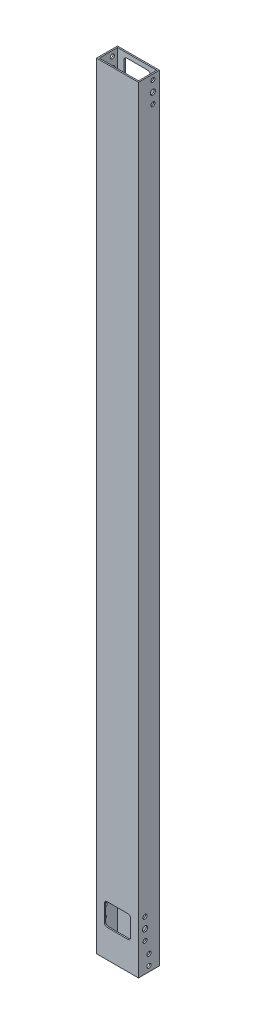
SolidWorks part; units mm, degrees
material "6061-T6 (SS)"
ref_plane "Front Plane" through (0, 0, 0) normal (0, 0, 1) x (1, 0, 0)
ref_plane "Top Plane" through (0, 0, 0) normal (0, 1, 0) x (1, 0, 0)
ref_plane "Right Plane" through (0, 0, 0) normal (1, 0, 0) x (0, 0, -1)
sketch "Sketch1" plane through (0, 0, 0) normal (0, 0, 1) x (1, 0, 0)
  line L1 (-25.4, -469.9) -> (25.4, -469.9)
  line L2 (-25.4, -469.9) -> (-25.4, 469.9)
  line L3 (-25.4, 469.9) -> (25.4, 469.9)
  line L4 (25.4, -469.9) -> (25.4, 469.9)
  line L5 (-25.4, -469.9) -> (25.4, 469.9) construction
  line L6 (-25.4, 469.9) -> (25.4, -469.9) construction
  point P0 (0, 0)
  dimension "D1" = 50.8
  dimension "D2" = 939.8
extrude "Boss-Extrude1" add sketch "Sketch1" along normal mid plane 25.4
shell "Shell1" thickness 1.5875 removed face at (0, -469.9, 0) removed face at (0, 469.9, 0)
sketch "Sketch3" plane through (0, 0, 0) normal (1, 0, 0) x (0, 0, -1)
  line L0 (-12.7, -469.9) -> (12.7, -469.9) construction
  circle A0 centre (0, -463.55) radius 2.4892
  circle A1 centre (0, -450.85) radius 2.4892
  point P6 (0, -469.9)
  dimension "D1" = 4.9784
  dimension "D2" = 6.35
  dimension "D3" = 12.7
extrude "Cut-Extrude1" cut sketch "Sketch3" against normal through all both and the other way through all
sketch "Sketch4" plane through (0, 0, 0) normal (1, 0, 0) x (0, 0, -1)
  line L4 (-12.7, -469.9) -> (12.7, -469.9) construction
  line L5 (-12.7, 469.9) -> (-12.7, -469.9) construction
  circle A3 centre (-4.7625, -422.275) radius 3.175
  circle A4 centre (-4.7625, -409.575) radius 2.4892
  circle A5 centre (-4.7625, -434.975) radius 2.4892
  dimension "D7" = 6.35
  dimension "D8" = 4.9784
  dimension "D9" = 12.7
  dimension "D10" = 12.7
  dimension "D11" = 47.625
  dimension "D12" = 7.9375
extrude "Cut-Extrude2" cut sketch "Sketch4" against normal through all both and the other way through all
sketch "Sketch5" plane through (0, 0, 0) normal (0, 0, 1) x (1, 0, 0)
  line L0 (-25.4, -469.9) -> (25.4, -469.9) construction
  line L1 (-15.875, -408.7812) -> (15.875, -408.7812)
  line L2 (-15.875, -408.7812) -> (-15.875, -435.7687)
  line L3 (-15.875, -435.7687) -> (15.875, -435.7687)
  line L4 (15.875, -408.7812) -> (15.875, -435.7687)
  point P4 (0, -435.7687)
  point P7 (0, -469.9)
  point P8 (15.875, -422.275)
  dimension "D1" = 31.75
  dimension "D2" = 26.9875
  dimension "D3" = 47.625
extrude "Cut-Extrude3" cut sketch "Sketch5" along normal through all
fillet "Fillet1" radius 3.175 4 edges at (-15.875, -435.7687, 11.9062) (15.875, -435.7687, 11.9062) (-15.875, -408.7812, 11.9062) (15.875, -408.7812, 11.9062)
sketch "Sketch6" plane through (0, 0, 0) normal (1, 0, 0) x (0, 0, -1)
  line L0 (12.7, 469.9) -> (12.7, -469.9) construction
  line L1 (-12.7, 469.9) -> (12.7, 469.9) construction
  circle A0 centre (4.7625, 450.85) radius 3.175
  circle A1 centre (4.7625, 463.55) radius 2.4892
  circle A2 centre (4.7625, 438.15) radius 2.4892
  dimension "D1" = 6.35
  dimension "D4" = 4.9784
  dimension "D2" = 7.9375
  dimension "D3" = 19.05
  dimension "D5" = 12.7
  dimension "D6" = 12.7
extrude "Cut-Extrude4" cut sketch "Sketch6" against normal through all both and the other way through all
sketch "Sketch7" plane through (0, 0, 0) normal (0, 0, 1) x (1, 0, 0)
  line L0 (25.4, 469.9) -> (-25.4, 469.9) construction
  line L1 (15.875, 464.3438) -> (-15.875, 464.3437)
  line L2 (15.875, 464.3438) -> (15.875, 437.3562)
  line L3 (15.875, 437.3562) -> (-15.875, 437.3562)
  line L4 (-15.875, 464.3437) -> (-15.875, 437.3562)
  point P4 (-16.0669, 449.12)
  point P5 (0, 464.3437)
  point P8 (0, 469.9)
  point P9 (-15.875, 450.85)
  dimension "D1" = 26.9875
  dimension "D2" = 31.75
  dimension "D3" = 19.05
extrude "Cut-Extrude5" cut sketch "Sketch7" against normal through all
fillet "Fillet2" radius 3.175 4 edges at (15.875, 437.3562, -11.9062) (-15.875, 437.3562, -11.9062) (-15.875, 464.3437, -11.9062) (15.875, 464.3438, -11.9062)
equation "\"D6@Sketch6\"=\"D5@Sketch6\""
